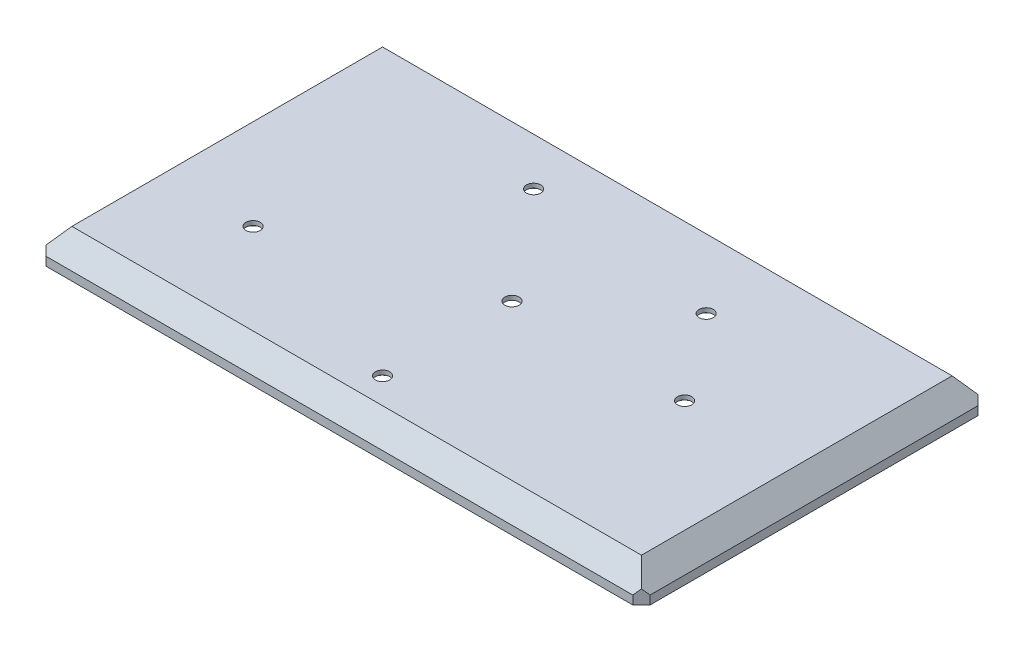
SolidWorks part; units mm, degrees
ref_plane "Front Plane" through (0, 0, 0) normal (0, 0, 1) x (1, 0, 0)
ref_plane "Top Plane" through (0, 0, 0) normal (0, 1, 0) x (1, 0, 0)
ref_plane "Right Plane" through (0, 0, 0) normal (1, 0, 0) x (0, 0, -1)
sketch "Sketch1" plane through (0, 0, 0) normal (0, 1, 0) x (1, 0, 0)
  line L1 (-70, -40) -> (70, -40)
  line L2 (-70, -40) -> (-70, 40)
  line L3 (-70, 40) -> (70, 40)
  line L4 (70, -40) -> (70, 40)
  line L5 (-70, -40) -> (70, 40) construction
  line L6 (-70, 40) -> (70, -40) construction
  point P0 (0, 0)
  dimension "D1" = 140
  dimension "D2" = 80
extrude "Boss-Extrude1" add sketch "Sketch1" along normal blind 2
sketch "Sketch2" plane through (0, 2, 0) normal (0, 1, 0) x (1, 0, 0)
  line L4 (70, -40) -> (70, 40)
  line L5 (70, 40) -> (-70, 40)
  line L6 (-70, 40) -> (-70, -40)
  line L7 (-70, -40) -> (70, -40)
  line L8 (70, -40) -> (70, 40)
  line L9 (70, 40) -> (-70, 40)
  line L10 (-70, 40) -> (-70, -40)
  line L11 (-70, -40) -> (70, -40)
  dimension "D1" = 0
ref_plane "Plane1" through (0, 7, 0) normal (0, 1, 0) x (1, 0, 0)
sketch "Sketch3" plane through (0, 7, 0) normal (0, 1, 0) x (1, 0, 0)
  line L0 (-70, 40) -> (-70, -40) construction
  line L1 (-66, -36) -> (66, -36)
  line L2 (-66, -36) -> (-66, 36)
  line L3 (-66, 36) -> (66, 36)
  line L4 (66, -36) -> (66, 36)
  line L5 (-66, -36) -> (66, 36) construction
  line L6 (-66, 36) -> (66, -36) construction
  line L7 (70, 40) -> (-70, 40) construction
  point P0 (0, 0)
  dimension "D1" = 4
  dimension "D2" = 4
loft "Loft1" add profiles "Sketch3", "Sketch2" connector at (-66, 7, 36) connector at (-70, 2, 40)
chamfer "Chamfer2" distance 2 angle 45 4 edges at (70, 1, 40) (70, 1, -40) (-70, 1, -40) (-70, 1, 40)
sketch "Sketch4" plane through (0, 0, 0) normal (0, -1, 0) x (1, 0, 0)
  line L0 (-70, -38) -> (-70, 38) construction
  line L1 (-62.9, 15) -> (-54.9, 15)
  line L2 (-62.9, 15) -> (-62.9, 25)
  line L3 (-62.9, 25) -> (-54.9, 25)
  line L4 (-54.9, 15) -> (-54.9, 25)
  line L5 (-62.9, 15) -> (-54.9, 25) construction
  line L6 (-62.9, 25) -> (-54.9, 15) construction
  line L7 (-70, 0) -> (70, 0) construction
  line L8 (70, 38) -> (70, -38) construction
  line L9 (0, 40) -> (0, -40) construction
  line L10 (-68, 40) -> (68, 40) construction
  line L11 (68, -40) -> (-68, -40) construction
  line L12 (-62.9, -25) -> (-54.9, -15) construction
  line L13 (-62.9, -15) -> (-54.9, -25) construction
  line L14 (-54.9, -15) -> (-54.9, -25)
  line L15 (-62.9, -25) -> (-54.9, -25)
  line L16 (-62.9, -15) -> (-62.9, -25)
  line L17 (-62.9, -15) -> (-54.9, -15)
  line L18 (62.9, -15) -> (54.9, -25) construction
  line L19 (62.9, -25) -> (54.9, -15) construction
  line L20 (62.9, 25) -> (54.9, 15) construction
  line L21 (62.9, 15) -> (54.9, 25) construction
  line L22 (62.9, -15) -> (54.9, -15)
  line L23 (62.9, -15) -> (62.9, -25)
  line L24 (62.9, -25) -> (54.9, -25)
  line L25 (54.9, -15) -> (54.9, -25)
  line L26 (54.9, 15) -> (54.9, 25)
  line L27 (62.9, 25) -> (54.9, 25)
  line L28 (62.9, 15) -> (62.9, 25)
  line L29 (62.9, 15) -> (54.9, 15)
  point P0 (-58.9, 20)
  point P21 (-58.9, -20)
  point P30 (58.9, -20)
  point P31 (58.9, 20)
  dimension "D1" = 10
  dimension "D2" = 7.1
  dimension "D3" = 8
  dimension "D4" = 40
extrude "Boss-Extrude2" add sketch "Sketch4" along normal blind 7
sketch "Sketch5" plane through (-62.9, 0, 0) normal (-1, 0, 0) x (0, 0, 1)
  line L0 (-15, 0) -> (-25, -7) construction
  line L1 (0, 0) -> (0, 50000) construction
  circle A0 centre (-20, -3.5) radius 2.05
  circle A1 centre (20, -3.5) radius 2.05
  dimension "D1" = 4.1
extrude "Cut-Extrude1" cut sketch "Sketch5" against normal through all
sketch "Sketch6" plane through (0, 0, 0) normal (0, -1, 0) x (1, 0, 0)
  line L0 (54.9, 25) -> (54.9, 15) construction
  line L1 (-53.9, -35) -> (53.9, -35)
  line L2 (-53.9, -35) -> (-53.9, 35)
  line L3 (-53.9, 35) -> (53.9, 35)
  line L4 (53.9, -35) -> (53.9, 35)
  line L5 (-53.9, -35) -> (53.9, 35) construction
  line L6 (-53.9, 35) -> (53.9, -35) construction
  line L8 (-66, 36) -> (66, 36) construction
  point P0 (0, 0)
  dimension "D1" = 1
  dimension "D2" = 1
extrude "Cut-Extrude2" cut sketch "Sketch6" against normal offset from surface (5 mm away) 2 up to face at (0, 7, 0)
sketch "Sketch7" plane through (0, 5, 0) normal (0, -1, 0) x (1, 0, 0)
  line L0 (0, 0) -> (0, 30) construction
  line L1 (0, 0) -> (40, 0) construction
  line L2 (0, 0) -> (25, -20) construction
  line L3 (0, 0) -> (-45, 15) construction
  line L4 (0, 0) -> (-20, -25) construction
  circle A0 centre (0, 30) radius 1.65
  circle A1 centre (40, 0) radius 1.65
  circle A2 centre (25, -20) radius 1.65
  circle A3 centre (-20, -25) radius 1.65
  circle A5 centre (-45, 15) radius 1.65
  circle A6 centre (0, 0) radius 1.65
  dimension "D1" = 3.3
  dimension "D5" = 20
  dimension "D6" = 45
  dimension "D2" = 30
  dimension "D3" = 40
  dimension "D4" = 25
  dimension "D7" = 20
  dimension "D8" = 25
  dimension "D9" = 15
extrude "Cut-Extrude3" cut sketch "Sketch7" against normal through all
sketch "Sketch8" plane through (0, 5, 0) normal (0, -1, 0) x (1, 0, 0)
  circle A0 centre (0, 30) radius 3
  circle A1 centre (40, 0) radius 3
  circle A2 centre (25, -20) radius 3
  circle A3 centre (0, 0) radius 3
  circle A4 centre (-45, 15) radius 3
  circle A5 centre (-20, -25) radius 3
  dimension "D1" = 6
extrude "Cut-Extrude4" cut sketch "Sketch8" against normal blind 1 and the other way through all
